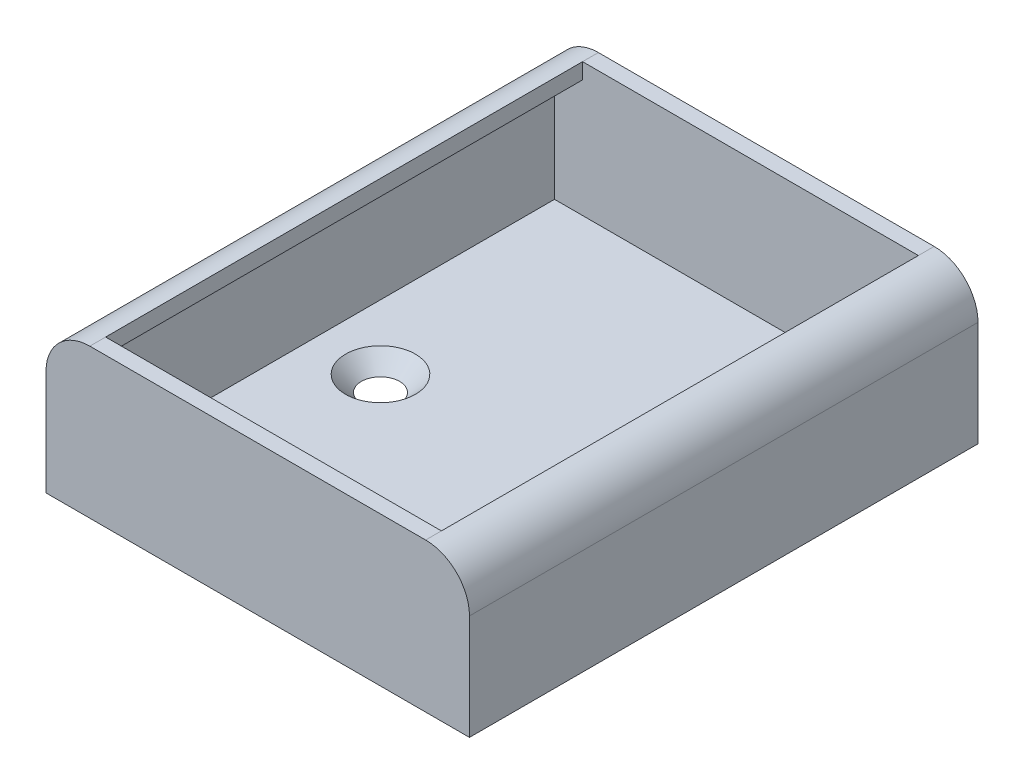
SolidWorks part; units mm, degrees
ref_plane "Front Plane" through (0, 0, 0) normal (0, 0, 1) x (1, 0, 0)
ref_plane "Top Plane" through (0, 0, 0) normal (0, 1, 0) x (1, 0, 0)
ref_plane "Right Plane" through (0, 0, 0) normal (1, 0, 0) x (0, 0, -1)
sketch "Sketch1" plane through (0, 0, 0) normal (0, 1, 0) x (1, 0, 0)
  line L1 (-24.15, -29) -> (24.15, -29)
  line L2 (-24.15, -29) -> (-24.15, 29)
  line L3 (-24.15, 29) -> (24.15, 29)
  line L4 (24.15, -29) -> (24.15, 29)
  line L5 (-24.15, -29) -> (24.15, 29) construction
  line L6 (-24.15, 29) -> (24.15, -29) construction
  point P0 (0, 0)
  dimension "D1" = 58
  dimension "D2" = 48.3
extrude "Boss-Extrude1" add sketch "Sketch1" along normal blind 17
fillet "Fillet1" radius 5 2 edges at (-24.15, 17, 0) (24.15, 17, 0)
shell "Shell2" thickness 1.8 removed face at (0, 17, 0)
sketch "Sketch2" plane through (0, 1.8, 0) normal (0, 1, 0) x (1, 0, 0)
  circle A0 centre (-15, 0) radius 1.75
  circle A1 centre (15, 0) radius 1.75
  dimension "D1" = 3.5
  dimension "D2" = 3.5
  dimension "D3" = 30
  dimension "D4" = 15
extrude "Cut-Extrude1" cut sketch "Sketch2" against normal blind 17
chamfer "Chamfer1" distance 2.23 angle 45 2 edges at (-15, 1.8, 1.75) (15, 1.8, 1.75)
